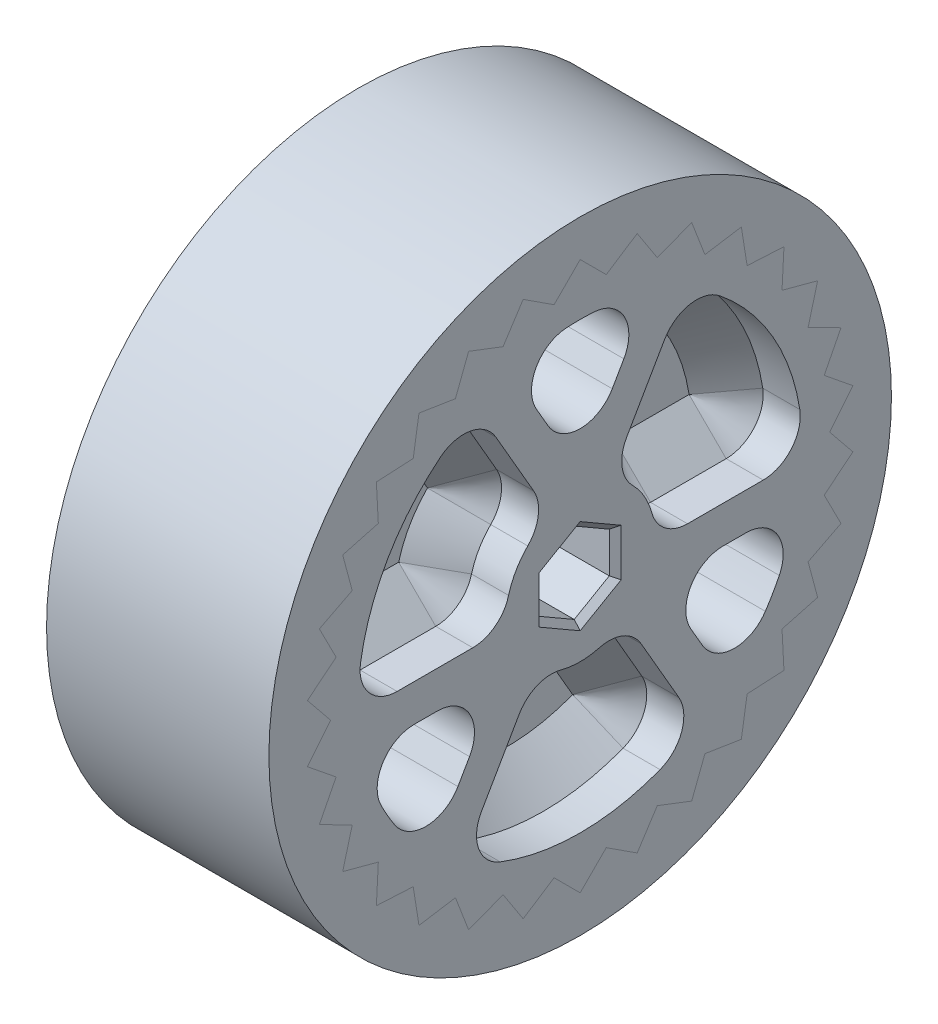
SolidWorks part; units mm, degrees
note: '?' marks a value the reader was unsure of.
other "WheelBody"
other "TPUOuter"
ref_plane "Front Plane" through (0, 0, 0) normal (0, 0, 1) x (1, 0, 0)
ref_plane "Top Plane" through (0, 0, 0) normal (0, 1, 0) x (1, 0, 0)
ref_plane "Right Plane" through (0, 0, 0) normal (1, 0, 0) x (0, 0, -1)
sketch "Sketch1" plane through (0, 0, 0) normal (1, 0, 0) x (0, 0, -1)
  circle A0 centre (0, 0) radius 25.4
  dimension "D1" = 50.8
extrude "Boss-Extrude2" add sketch "Sketch1" along normal mid plane 6.35
sketch "Sketch3" plane through (0, 0, 0) normal (1, 0, 0) x (0, 0, -1)
  circle A0 centre (0, 0) radius 6.35
  dimension "D1" = 12.7
extrude "Boss-Extrude3" add sketch "Sketch3" against normal mid plane 19.05
ref_axis "Axis1" through (0, 0, 0) along (1, 0, 0)?
sketch "Sketch5" plane through (9.525, 0, 0) normal (1, 0, 0) x (0, 0, -1)
  line L0 (0, 25.3821) -> (0, 34.0271) construction
  line L2 (-5.9601, 18.0936) -> (0, 7.7705)
  line L3 (-2.54, 5.8199) -> (-8.9033, 16.8414)
  line L5 (2.54, 5.8199) -> (8.9033, 16.8414)
  line L7 (0, 0) -> (23.8682, 8.6873) construction
  line L8 (17.9011, 6.5155) -> (23.8682, 8.6873)
  line L9 (8.9033, 16.8414) -> (12.08, 22.3436) construction
  line L10 (-18.046, 6.1028) -> (-23.9412, 8.4841)
  line L11 (-8.9033, 16.8414) -> (-12.08, 22.3436) construction
  line L12 (-2.54, 5.8199) -> (2.54, 5.8199)
  line L13 (0, 7.7705) -> (5.9601, 18.0936)
  arc A1 (-8.9033, 16.8414) -> (-18.046, 6.1028) centre (0, 0) ccw
  arc A4 (5.9601, 18.0936) -> (-5.9601, 18.0936) centre (0, 0) ccw
  arc A5 (-12.08, 22.3436) -> (12.08, 22.3436) centre (0, 0) cw
  circle A6 centre (0, 0) radius 25.4 construction
  arc A8 (-12.08, 22.3436) -> (-23.9412, 8.4841) centre (0, 0) ccw
  arc A11 (12.08, 22.3436) -> (23.8682, 8.6873) centre (0, 0) cw
  arc A12 (8.9033, 16.8414) -> (17.9011, 6.5155) centre (0, 0) cw
  circle A13 centre (0, 0) radius 6.35 construction
  circle A14 centre (0, 0) radius 6.35 construction
  point P2 (0, 0)
  point P8 (10.0445, 19.8257)
  dimension "D1" = 3.175
  dimension "D2" = 3.175
  dimension "D3" = 5.08
  dimension "D5" = 60
  dimension "D9" = 6.35
extrude "Boss-Extrude4" add sketch "Sketch5" against normal up to surface (19.05 mm away)
pattern_circular "CirPattern5" count 3 over 360 about axis through (0, 0, 0) along (1, 0, 0) of "Boss-Extrude4"
fillet "Fillet1" radius 3.175 21 edges at (6.35, -0.7102, 19.0368) (6.35, -0.7102, 6.3102) (6.35, -5.1096, 3.7702) (6.35, -16.1312, 10.1335) (6.35, -3.8852, 18.6496) (6.35, -14.2084, 12.6895) (6.35, -3.8852, 6.7294) (6.35, -16.1312, -10.1335) (6.35, -5.1096, -3.7702) (6.35, -0.7102, -6.3102) (6.35, -0.7102, -19.0368) (6.35, -14.2084, -12.6895) (6.35, -3.8852, -18.6496) (6.35, -3.8852, -6.7294) (6.35, 16.8414, -8.9033) (6.35, 5.8199, -2.54) (6.35, 5.8199, 2.54) (6.35, 16.8414, 8.9033) (6.35, 18.0936, -5.9601) (6.35, 18.0936, 5.9601) (6.35, 7.7705, 0)
fillet "Fillet2" radius 3.175 21 edges at (-6.35, -16.1312, 10.1335) (-6.35, -3.8852, 18.6496) (-6.35, -14.2084, 12.6895) (-6.35, -3.8852, 6.7294) (-6.35, -14.2084, -12.6895) (-6.35, -3.8852, -18.6496) (-6.35, -3.8852, -6.7294) (-6.35, -0.7102, 19.0368) (-6.35, -0.7102, 6.3102) (-6.35, -5.1096, 3.7702) (-6.35, -16.1312, -10.1335) (-6.35, -5.1096, -3.7702) (-6.35, -0.7102, -6.3102) (-6.35, -0.7102, -19.0368) (-6.35, 16.8414, 8.9033) (-6.35, 18.0936, -5.9601) (-6.35, 18.0936, 5.9601) (-6.35, 7.7705, 0) (-6.35, 16.8414, -8.9033) (-6.35, 5.8199, -2.54) (-6.35, 5.8199, 2.54)
sketch "Sketch6" plane through (9.525, 0, 0) normal (1, 0, 0) x (0, 0, -1)
  line L1 (0, 3.4641) -> (-3, 1.7321)
  line L2 (-3, 1.7321) -> (-3, -1.7321)
  line L3 (-3, -1.7321) -> (0, -3.4641)
  line L4 (0, -3.4641) -> (3, -1.7321)
  line L5 (3, -1.7321) -> (3, 1.7321)
  line L6 (3, 1.7321) -> (0, 3.4641)
  circle A0 centre (0, 0) radius 3 construction
  dimension "D1" = 6
extrude "Cut-Extrude2" cut sketch "Sketch6" against normal through all both and the other way through all
chamfer "Chamfer1" distance 3.175 angle 45 48 edges at (3.175, 3.175, 5.4993) (3.175, -0.7102, 12.4415) (3.175, 11.1298, 5.6057) (3.175, 9.525, 16.4978) (3.175, 0.4013, 18.0956) (3.175, 15.4705, 9.3953) (3.175, 6.321, 3.587) (3.175, -0.0541, 7.2677) (3.175, -0.7102, -12.4415) (3.175, 3.175, -5.4993) (3.175, 9.525, -16.4978) (3.175, 11.1298, -5.6057) (3.175, 15.4705, -9.3953) (3.175, 0.4013, -18.0956) (3.175, 6.321, -3.587) (3.175, -0.0541, -7.2677) (3.175, -6.35, 0) (3.175, -10.4196, -6.8358) (3.175, -10.4196, 6.8358) (3.175, -19.05, 0) (3.175, -15.8719, -8.7002) (3.175, -15.8719, 8.7002) (3.175, -6.267, 3.6807) (3.175, -6.267, -3.6807) (-3.175, -0.7102, -12.4415) (-3.175, 3.175, -5.4993) (-3.175, 11.1298, -5.6057) (-3.175, 9.525, -16.4978) (-3.175, 15.4705, -9.3953) (-3.175, 0.4013, -18.0956) (-3.175, 6.321, -3.587) (-3.175, -0.0541, -7.2677) (-3.175, -10.4196, 6.8358) (-3.175, -6.35, 0) (-3.175, -10.4196, -6.8358) (-3.175, -19.05, 0) (-3.175, -15.8719, 8.7002) (-3.175, -15.8719, -8.7002) (-3.175, -6.267, -3.6807) (-3.175, -6.267, 3.6807) (-3.175, 11.1298, 5.6057) (-3.175, 3.175, 5.4993) (-3.175, -0.7102, 12.4415) (-3.175, 9.525, 16.4978) (-3.175, 15.4705, 9.3953) (-3.175, 0.4013, 18.0956) (-3.175, -0.0541, 7.2677) (-3.175, 6.321, 3.587)
chamfer "ShaftChamfer" distance 0.508 angle 45 12 edges at (9.525, 0, -3) (-9.525, 0, -3) (9.525, -2.5981, 1.5) (-9.525, -2.5981, 1.5) (9.525, -2.5981, -1.5) (-9.525, -2.5981, -1.5) (9.525, 0, 3) (-9.525, 0, 3) (9.525, 2.5981, 1.5) (-9.525, 2.5981, 1.5) (9.525, 2.5981, -1.5) (-9.525, 2.5981, -1.5)
sketch "Sketch8" plane through (-9.525, 0, 0) normal (-1, 0, 0) x (0, 0, 1)
  circle A0 centre (0, 0) radius 26.67
  circle A1 centre (0, 0) radius 12.7
  dimension "D1" = 53.34
  dimension "D2" = 25.4
extrude "Boss-Extrude5" add sketch "Sketch8" against normal up to surface (19.05 mm away) separate body
sketch "Sketch9" plane through (-9.525, 0, 0) normal (-1, 0, 0) x (0, 0, 1)
  line L0 (0, 0) -> (0, 23.495) construction
  line L1 (-2.54, 20.955) -> (0, 23.495)
  line L2 (0, 23.495) -> (2.54, 20.955)
  line L3 (2.54, 20.955) -> (0, 0)
  line L4 (-2.54, 20.955) -> (0, 0)
  line L5 (-6.766, 26.67) -> (10.6632, 26.67) construction
  circle A1 centre (0, 0) radius 26.67 construction
  dimension "D1" = 90
  dimension "D2" = 2.54
  dimension "D3" = 3.175
extrude "Cut-Extrude3" cut sketch "Sketch9" against normal through all both and the other way through all
pattern_circular "CirPattern9" count 30 over 360 about axis through (0, 0, 0) along (1, 0, 0) of "Cut-Extrude3"
sketch "Sketch10" plane through (9.525, 0, 0) normal (1, 0, 0) x (0, 0, -1)
  line L60 (4.8849, 22.9816) -> (2.2346, 21.2604)
  line L61 (6.606, 20.3313) -> (4.8849, 22.9816)
  line L62 (9.5563, 21.4638) -> (6.606, 20.3313)
  line L63 (10.6888, 18.5135) -> (9.5563, 21.4638)
  line L64 (13.81, 19.0079) -> (10.6888, 18.5135)
  line L65 (14.3044, 15.8866) -> (13.81, 19.0079)
  line L66 (17.4602, 15.7212) -> (14.3044, 15.8866)
  line L67 (17.2948, 12.5654) -> (17.4602, 15.7212)
  line L68 (20.3473, 11.7475) -> (17.2948, 12.5654)
  line L69 (19.5294, 8.695) -> (20.3473, 11.7475)
  line L70 (22.3451, 7.2604) -> (19.5294, 8.695)
  line L71 (20.9104, 4.4446) -> (22.3451, 7.2604)
  line L72 (23.3663, 2.4559) -> (20.9104, 4.4446)
  line L73 (21.3775, 0) -> (23.3663, 2.4559)
  line L74 (23.3663, -2.4559) -> (21.3775, 0)
  line L75 (20.9104, -4.4446) -> (23.3663, -2.4559)
  line L76 (22.3451, -7.2604) -> (20.9104, -4.4446)
  line L77 (19.5294, -8.695) -> (22.3451, -7.2604)
  line L78 (20.3473, -11.7475) -> (19.5294, -8.695)
  line L79 (17.2948, -12.5654) -> (20.3473, -11.7475)
  line L80 (17.4602, -15.7212) -> (17.2948, -12.5654)
  line L81 (14.3044, -15.8866) -> (17.4602, -15.7212)
  line L82 (13.81, -19.0079) -> (14.3044, -15.8866)
  line L83 (10.6888, -18.5135) -> (13.81, -19.0079)
  line L84 (9.5563, -21.4638) -> (10.6888, -18.5135)
  line L85 (6.606, -20.3313) -> (9.5563, -21.4638)
  line L86 (4.8849, -22.9816) -> (6.606, -20.3313)
  line L87 (2.2346, -21.2604) -> (4.8849, -22.9816)
  line L88 (0, -23.495) -> (2.2346, -21.2604)
  line L89 (-2.2346, -21.2604) -> (0, -23.495)
  line L90 (-4.8849, -22.9816) -> (-2.2346, -21.2604)
  line L91 (-6.606, -20.3313) -> (-4.8849, -22.9816)
  line L92 (-9.5563, -21.4638) -> (-6.606, -20.3313)
  line L93 (-10.6888, -18.5135) -> (-9.5563, -21.4638)
  line L94 (-13.81, -19.0079) -> (-10.6888, -18.5135)
  line L95 (-14.3044, -15.8866) -> (-13.81, -19.0079)
  line L96 (-17.4602, -15.7212) -> (-14.3044, -15.8866)
  line L97 (-17.2948, -12.5654) -> (-17.4602, -15.7212)
  line L98 (-20.3473, -11.7475) -> (-17.2948, -12.5654)
  line L99 (-19.5294, -8.695) -> (-20.3473, -11.7475)
  line L100 (-22.3451, -7.2604) -> (-19.5294, -8.695)
  line L101 (-20.9104, -4.4446) -> (-22.3451, -7.2604)
  line L102 (-23.3663, -2.4559) -> (-20.9104, -4.4446)
  line L103 (-21.3775, 0) -> (-23.3663, -2.4559)
  line L104 (-23.3663, 2.4559) -> (-21.3775, 0)
  line L105 (-20.9104, 4.4446) -> (-23.3663, 2.4559)
  line L106 (-22.3451, 7.2604) -> (-20.9104, 4.4446)
  line L107 (-19.5294, 8.695) -> (-22.3451, 7.2604)
  line L108 (-20.3473, 11.7475) -> (-19.5294, 8.695)
  line L109 (-17.2948, 12.5654) -> (-20.3473, 11.7475)
  line L110 (-17.4602, 15.7212) -> (-17.2948, 12.5654)
  line L111 (-14.3044, 15.8866) -> (-17.4602, 15.7212)
  line L112 (-13.81, 19.0079) -> (-14.3044, 15.8866)
  line L113 (-10.6888, 18.5135) -> (-13.81, 19.0079)
  line L114 (-9.5563, 21.4638) -> (-10.6888, 18.5135)
  line L115 (-6.606, 20.3313) -> (-9.5563, 21.4638)
  line L116 (-4.8849, 22.9816) -> (-6.606, 20.3313)
  line L117 (-2.2346, 21.2604) -> (-4.8849, 22.9816)
  line L118 (0, 23.495) -> (-2.2346, 21.2604)
  line L119 (2.2346, 21.2604) -> (0, 23.495)
  line L120 (4.8849, 22.9816) -> (2.2346, 21.2604)
  line L121 (6.606, 20.3313) -> (4.8849, 22.9816)
  line L122 (9.5563, 21.4638) -> (6.606, 20.3313)
  line L123 (10.6888, 18.5135) -> (9.5563, 21.4638)
  line L124 (13.81, 19.0079) -> (10.6888, 18.5135)
  line L125 (14.3044, 15.8866) -> (13.81, 19.0079)
  line L126 (17.4602, 15.7212) -> (14.3044, 15.8866)
  line L127 (17.2948, 12.5654) -> (17.4602, 15.7212)
  line L128 (20.3473, 11.7475) -> (17.2948, 12.5654)
  line L129 (19.5294, 8.695) -> (20.3473, 11.7475)
  line L130 (22.3451, 7.2604) -> (19.5294, 8.695)
  line L131 (20.9104, 4.4446) -> (22.3451, 7.2604)
  line L132 (23.3663, 2.4559) -> (20.9104, 4.4446)
  line L133 (21.3775, 0) -> (23.3663, 2.4559)
  line L134 (23.3663, -2.4559) -> (21.3775, 0)
  line L135 (20.9104, -4.4446) -> (23.3663, -2.4559)
  line L136 (22.3451, -7.2604) -> (20.9104, -4.4446)
  line L137 (19.5294, -8.695) -> (22.3451, -7.2604)
  line L138 (20.3473, -11.7475) -> (19.5294, -8.695)
  line L139 (17.2948, -12.5654) -> (20.3473, -11.7475)
  line L140 (17.4602, -15.7212) -> (17.2948, -12.5654)
  line L141 (14.3044, -15.8866) -> (17.4602, -15.7212)
  line L142 (13.81, -19.0079) -> (14.3044, -15.8866)
  line L143 (10.6888, -18.5135) -> (13.81, -19.0079)
  line L144 (9.5563, -21.4638) -> (10.6888, -18.5135)
  line L145 (6.606, -20.3313) -> (9.5563, -21.4638)
  line L146 (4.8849, -22.9816) -> (6.606, -20.3313)
  line L147 (2.2346, -21.2604) -> (4.8849, -22.9816)
  line L148 (0, -23.495) -> (2.2346, -21.2604)
  line L149 (-2.2346, -21.2604) -> (0, -23.495)
  line L150 (-4.8849, -22.9816) -> (-2.2346, -21.2604)
  line L151 (-6.606, -20.3313) -> (-4.8849, -22.9816)
  line L152 (-9.5563, -21.4638) -> (-6.606, -20.3313)
  line L153 (-10.6888, -18.5135) -> (-9.5563, -21.4638)
  line L154 (-13.81, -19.0079) -> (-10.6888, -18.5135)
  line L155 (-14.3044, -15.8866) -> (-13.81, -19.0079)
  line L156 (-17.4602, -15.7212) -> (-14.3044, -15.8866)
  line L157 (-17.2948, -12.5654) -> (-17.4602, -15.7212)
  line L158 (-20.3473, -11.7475) -> (-17.2948, -12.5654)
  line L159 (-19.5294, -8.695) -> (-20.3473, -11.7475)
  line L160 (-22.3451, -7.2604) -> (-19.5294, -8.695)
  line L161 (-20.9104, -4.4446) -> (-22.3451, -7.2604)
  line L162 (-23.3663, -2.4559) -> (-20.9104, -4.4446)
  line L163 (-21.3775, 0) -> (-23.3663, -2.4559)
  line L164 (-23.3663, 2.4559) -> (-21.3775, 0)
  line L165 (-20.9104, 4.4446) -> (-23.3663, 2.4559)
  line L166 (-22.3451, 7.2604) -> (-20.9104, 4.4446)
  line L167 (-19.5294, 8.695) -> (-22.3451, 7.2604)
  line L168 (-20.3473, 11.7475) -> (-19.5294, 8.695)
  line L169 (-17.2948, 12.5654) -> (-20.3473, 11.7475)
  line L170 (-17.4602, 15.7212) -> (-17.2948, 12.5654)
  line L171 (-14.3044, 15.8866) -> (-17.4602, 15.7212)
  line L172 (-13.81, 19.0079) -> (-14.3044, 15.8866)
  line L173 (-10.6888, 18.5135) -> (-13.81, 19.0079)
  line L174 (-9.5563, 21.4638) -> (-10.6888, 18.5135)
  line L175 (-6.606, 20.3313) -> (-9.5563, 21.4638)
  line L176 (-4.8849, 22.9816) -> (-6.606, 20.3313)
  line L177 (-2.2346, 21.2604) -> (-4.8849, 22.9816)
  line L178 (0, 23.495) -> (-2.2346, 21.2604)
  line L179 (2.2346, 21.2604) -> (0, 23.495)
  circle A1 centre (0, 0) radius 26.67
  circle A2 centre (0, 0) radius 26.67
  dimension "D1" = 0
  dimension "D2" = 0
extrude "Cut-Extrude4" cut sketch "Sketch10" against normal through all both and the other way through all
